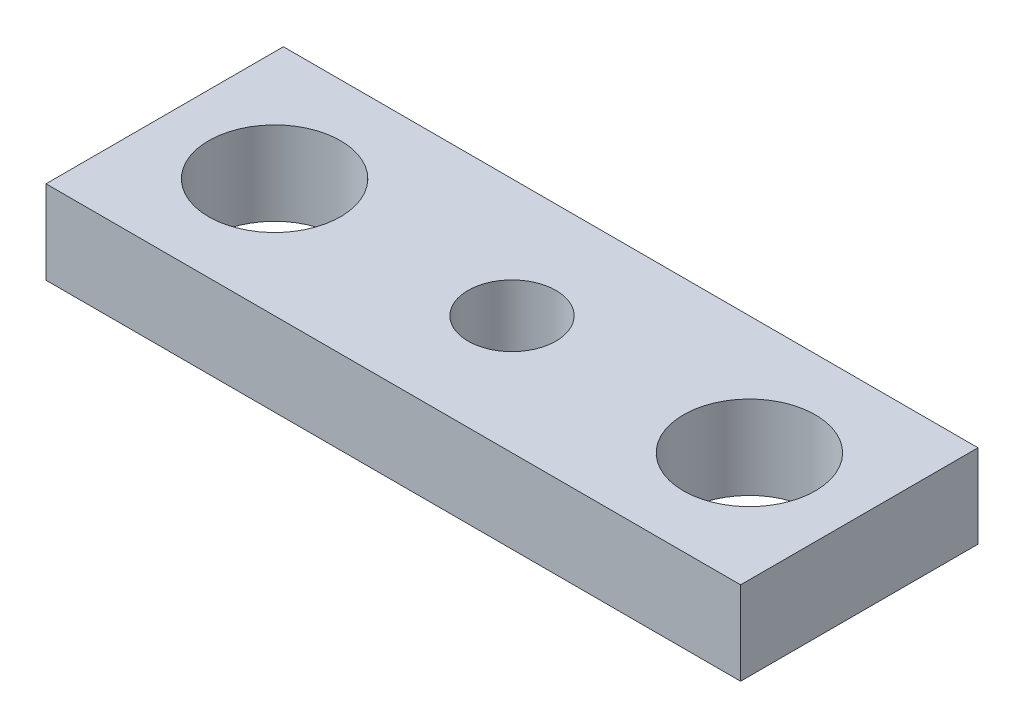
SolidWorks part; units mm, degrees
ref_plane "前视基准面" through (0, 0, 0) normal (0, 0, 1) x (1, 0, 0)
ref_plane "上视基准面" through (0, 0, 0) normal (0, 1, 0) x (1, 0, 0)
ref_plane "右视基准面" through (0, 0, 0) normal (1, 0, 0) x (0, 0, -1)
sketch "草图1" plane through (0, 0, 0) normal (0, 1, 0) x (1, 0, 0)
  line L1 (-39.5, 13.5) -> (39.5, 13.5)
  line L2 (-39.5, 13.5) -> (-39.5, -13.5)
  line L3 (-39.5, -13.5) -> (39.5, -13.5)
  line L4 (39.5, 13.5) -> (39.5, -13.5)
  line L5 (-39.5, 13.5) -> (39.5, -13.5) construction
  line L6 (-39.5, -13.5) -> (39.5, 13.5) construction
  point P0 (0, 0)
  dimension "D1" = 79
  dimension "D2" = 27
extrude "凸台-拉伸1" add sketch "草图1" along normal blind 9.5
sketch "草图2" plane through (0, 0, 0) normal (0, -1, 0) x (1, 0, 0)
  line L0 (-39.5, 0) -> (39.5, 0) construction
  line L1 (-39.5, -13.5) -> (-39.5, 13.5) construction
  line L2 (39.5, 13.5) -> (39.5, -13.5) construction
ref_plane "基准面1" through (0, 0, 0) normal (0, 0, 1) x (1, 0, 0)
sketch "草图3" plane through (0, 9.5, 0) normal (0, 1, 0) x (1, 0, 0)
  line L0 (-14.85, 0) -> (14.85, 0) construction
  line L1 (0, 13.5) -> (0, -13.5) construction
  line L2 (39.5, 13.5) -> (-39.5, 13.5) construction
  line L3 (-39.5, -13.5) -> (39.5, -13.5) construction
  circle A0 centre (-27, 0) radius 7.5
  circle A1 centre (27, 0) radius 7.5
  dimension "D1" = 15
  dimension "D2" = 54
extrude "切除-拉伸1" cut sketch "草图3" against normal through all contours A1 | A0
sketch "草图7" plane through (-39.5, 0, 0) normal (-1, 0, 0) x (0, 0, 1)
  line L0 (-13.5, 4.75) -> (13.5, 4.75) construction
  line L1 (-13.5, 9.5) -> (-13.5, 0) construction
  line L2 (13.5, 9.5) -> (13.5, 0) construction
ref_plane "基准面3" through (0, 4.75, 0) normal (0, 1, 0) x (1, 0, 0)
sketch "草图9" plane through (0, 4.75, 0) normal (0, 1, 0) x (1, 0, 0)
  line L0 (-44.1863, 9.5) -> (43.8901, 9.5) construction
  line L1 (39.5, 13.5) -> (-39.5, 13.5) construction
  line L2 (-39.5, -9.5) -> (39.6508, -9.5) construction
  line L3 (-39.5, 13.5) -> (-39.5, -13.5) construction
  line L4 (-39.5, -13.5) -> (39.5, -13.5) construction
  dimension "D1" = 4
  dimension "D2" = 4
sketch "草图10" plane through (0, 0, 0) normal (0, -1, 0) x (1, 0, 0)
  circle A0 centre (0, 0) radius 5
  dimension "D1" = 10
extrude "切除-拉伸2" cut sketch "草图10" against normal through all
